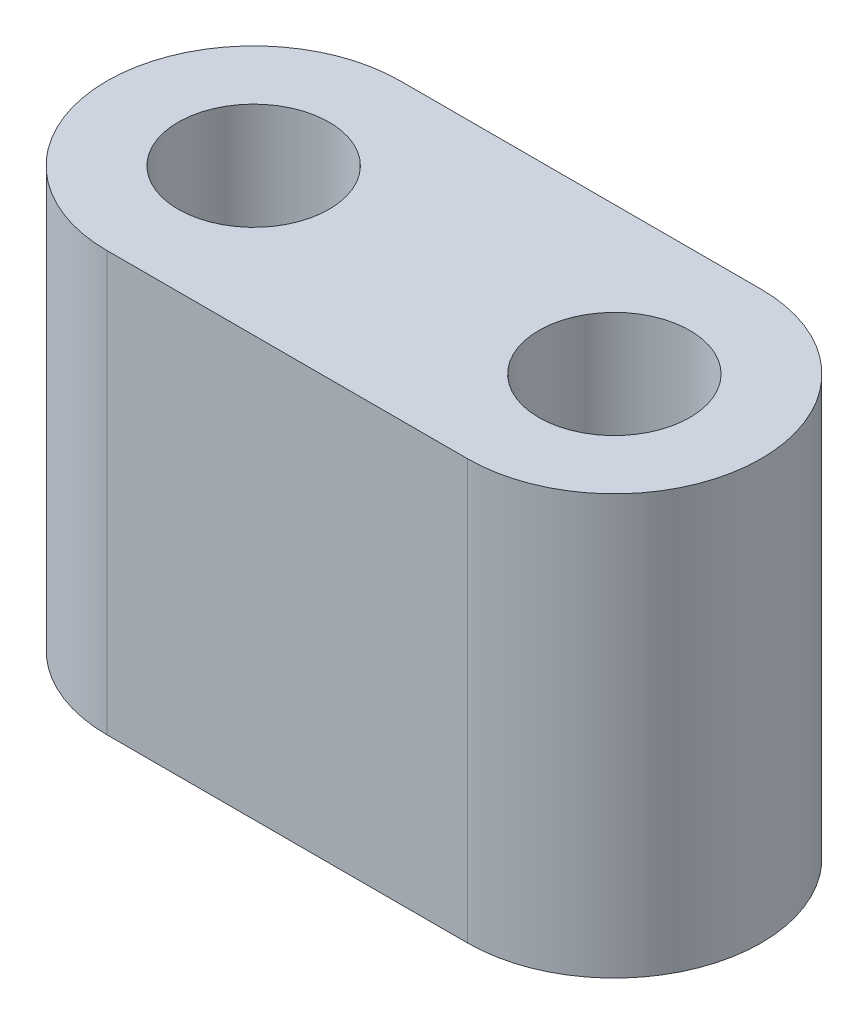
SolidWorks part; units mm, degrees
material "ABS"
ref_plane "Front" through (0, 0, 0) normal (0, 0, 1) x (1, 0, 0)
ref_plane "Top" through (0, 0, 0) normal (0, 1, 0) x (1, 0, 0)
ref_plane "Right" through (0, 0, 0) normal (1, 0, 0) x (0, 0, -1)
ref_axis "X" through (-80.9, 0, 0) along (1, 0, 0)
ref_axis "Y" through (0, -50, 0) along (0, 1, 0)
ref_axis "Z" through (0, 0, -80.9) along (0, 0, 1)
sketch "Sketch1" plane through (0, 0, 0) normal (0, 1, 0) x (1, 0, 0)
  line L0 (-4.3, 0) -> (4.3, 0) construction
  line L1 (-4.3, 3.5) -> (4.3, 3.5)
  line L2 (-4.3, -3.5) -> (4.3, -3.5)
  arc A0 (-4.3, 3.5) -> (-4.3, -3.5) centre (-4.3, 0) ccw
  arc A1 (4.3, -3.5) -> (4.3, 3.5) centre (4.3, 0) ccw
  circle A2 centre (-4.3, 0) radius 1.8
  circle A3 centre (4.3, 0) radius 1.8
  point P3 (0, 0)
  point P12 (12.708, 0)
  point P13 (0, 0)
  point P14 (0, 0)
  point P15 (0, 0)
  dimension "D2" = 3.6
  dimension "D3" = 5
  dimension "D1" = 7
extrude "Boss-Extrude1" add sketch "Sketch1" along normal mid plane 10
